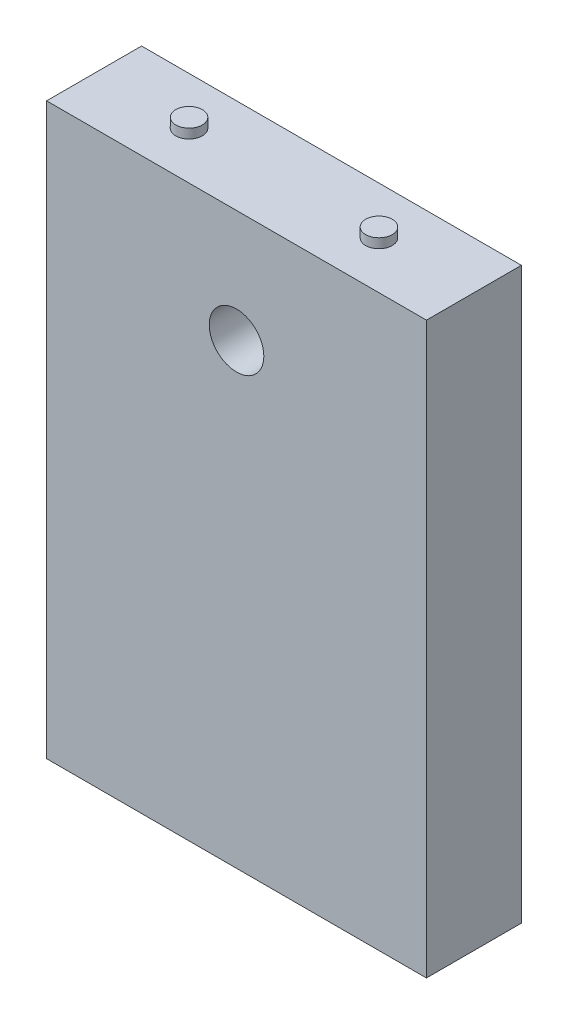
SolidWorks part; units mm, degrees
ref_plane "Front Plane" through (0, 0, 0) normal (0, 0, 1) x (1, 0, 0)
ref_plane "Top Plane" through (0, 0, 0) normal (0, 1, 0) x (1, 0, 0)
ref_plane "Right Plane" through (0, 0, 0) normal (1, 0, 0) x (0, 0, -1)
sketch "Sketch1" plane through (0, 0, 0) normal (0, 0, 1) x (1, 0, 0)
  line L0 (0, 28.6148) -> (0, -31.3852) construction
  line L1 (-20, 28.6148) -> (20, 28.6148)
  line L2 (-20, 28.6148) -> (-20, -31.3852)
  line L3 (-20, -31.3852) -> (20, -31.3852)
  line L4 (20, 28.6148) -> (20, -31.3852)
  line L5 (-20, 16.7548) -> (20, 16.7548) construction
  circle A0 centre (0, 16.7548) radius 2.875
  point P0 (0, 0)
  dimension "D4" = 5.75
  dimension "D1" = 40
  dimension "D2" = 60
  dimension "D3" = 11.86
extrude "Boss-Extrude1" add sketch "Sketch1" along normal blind 10
sketch "Sketch5" plane through (0, 28.6148, 0) normal (0, 1, 0) x (1, 0, 0)
  line L0 (0, 0) -> (0, -10) construction
  line L1 (20, -10) -> (-20, -10) construction
  line L2 (-20, -5) -> (20, -5) construction
  line L3 (-20, -10) -> (-20, 0) construction
  line L4 (20, -10) -> (20, 0) construction
  line L5 (-10, -10) -> (-10, 0) construction
  line L6 (20, 0) -> (-20, 0) construction
  line L7 (10, -10) -> (10, 0) construction
  circle A0 centre (-10, -5) radius 1.4
  circle A1 centre (10, -5) radius 1.4
  point P11 (-10, -5)
  point P12 (10, -5)
  point P18 (-10, -5)
  dimension "D2" = 2.8
  dimension "D1" = 20
extrude "Boss-Extrude2" add sketch "Sketch5" along normal blind 1
sketch "Sketch6" plane through (0, -31.3852, 0) normal (0, -1, 0) x (-1, 0, 0)
  line L0 (0, 0) -> (0, -10) construction
  line L1 (20, 0) -> (-20, 0) construction
  line L2 (20, -10) -> (-20, -10) construction
  line L3 (20, -5) -> (-20, -5) construction
  line L4 (20, -10) -> (20, 0) construction
  line L5 (-20, -10) -> (-20, 0) construction
  line L6 (10, 0) -> (10, -10) construction
  line L7 (-10, 0) -> (-10, -10) construction
  circle A0 centre (10, -5) radius 1.4
  circle A1 centre (-10, -5) radius 1.4
  point P12 (10, -5)
  point P13 (-10, -5)
  point P17 (10, -5)
  dimension "D2" = 2.8
  dimension "D1" = 20
extrude "Boss-Extrude3" add sketch "Sketch6" along normal blind 1
